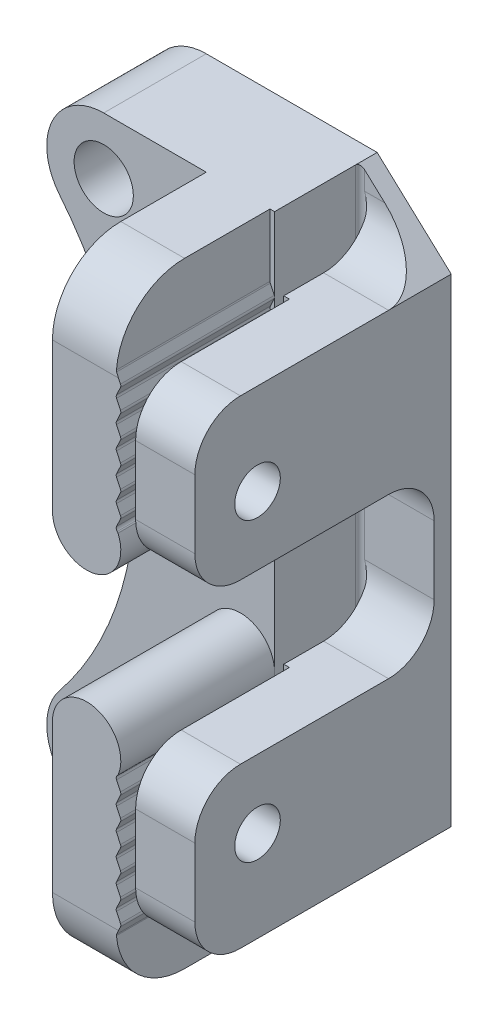
SolidWorks part; units mm, degrees
ref_plane "Front Plane" through (0, 0, 0) normal (0, 0, 1) x (1, 0, 0)
ref_plane "Top Plane" through (0, 0, 0) normal (0, 1, 0) x (1, 0, 0)
ref_plane "Right Plane" through (0, 0, 0) normal (1, 0, 0) x (0, 0, -1)
sketch "Sketch1" plane through (0, 0, 0) normal (0, 0, 1) x (1, 0, 0)
  line L1 (-10, 27) -> (5, 27)
  line L3 (-10, -27) -> (5, -27)
  line L4 (5, 27) -> (5, -27)
  circle A0 centre (0, 0) radius 2.6
  circle A1 centre (-10, 22) radius 2.6
  circle A2 centre (-10, -22) radius 2.6
  arc A3 (-13.8888, -18.8571) -> (-10, -27) centre (-10, -22) ccw
  arc A4 (-10, 27) -> (-13.8888, 18.8571) centre (-10, 22) ccw
  arc A5 (-13.8888, 18.8571) -> (-13.8888, -18.8571) centre (-37.2213, 0) cw
  dimension "D6" = 5.2
  dimension "D9" = 5
  dimension "D5" = 30
  dimension "D1" = 5
  dimension "D2" = 27
  dimension "D3" = 27
  dimension "D4" = 10
extrude "Boss-Extrude1" add sketch "Sketch1" along normal blind 9
sketch "Sketch2" plane through (0, 0, 9) normal (0, 0, 1) x (1, 0, 0)
  line L0 (5, -27) -> (5, 27) construction
  line L1 (5, -27) -> (5, -8)
  line L2 (5, 27) -> (-10, 27) construction
  line L3 (-10, -27) -> (5, -27) construction
  line L4 (5, 27) -> (-1, 27)
  line L5 (-1, -27) -> (5, -27)
  line L6 (-1, 8) -> (-1, 27)
  line L7 (-1, -8) -> (-1, -27)
  line L8 (5, 8) -> (5, 27)
  arc A0 (-1, 8) -> (5, 8) centre (2, 8) ccw
  arc A1 (5, -8) -> (-1, -8) centre (2, -8) ccw
  dimension "D2" = 10
  dimension "D1" = 6
  dimension "D3" = 5
extrude "Boss-Extrude2" add sketch "Sketch2" along normal offset from surface (13.5 mm away) 22.5 up to face at (-7.4, 22, 0)
sketch "Sketch3" plane through (5, 0, 0) normal (1, 0, 0) x (0, 0, -1)
  line L1 (0, -27) -> (0, 27) construction
  circle A0 centre (-17, 13) radius 2.6
  circle A1 centre (-5, 13) radius 2.6 construction
  circle A2 centre (-17, -13) radius 2.6
  circle A3 centre (-5, -13) radius 2.6 construction
  dimension "D5" = 5.2
  dimension "D1" = 13
  dimension "D2" = 13
  dimension "D3" = 5
  dimension "D4" = 12
extrude "Cut-Extrude1" cut sketch "Sketch3" against normal blind 30
fillet "Fillet1" radius 6 2 edges at (2, -27, 22.5) (2, 27, 22.5)
chamfer "Chamfer1" distance 1 angle 45 3 edges at (-7.4, 22, 0) (2.6, 0, 0) (-7.4, -22, 0)
sketch "Sketch4" plane through (0, 0, 0) normal (0, 0, -1) x (-1, 0, 0)
  line L0 (-5, 27) -> (-11.5, 21)
  line L1 (-11.5, 21) -> (-11.5, -21)
  line L2 (-11.5, -21) -> (-5, -27)
  line L3 (-5, -27) -> (-5, 27) construction
  line L5 (-5, 27) -> (-5, -27)
  arc A0 (-5, 8) -> (1, 8) centre (-2, 8) ccw construction
  arc A1 (1, -8) -> (-5, -8) centre (-2, -8) ccw construction
  point P10 (-2, -5)
  dimension "D2" = 16
  dimension "D1" = 6.5
  dimension "D3" = 16
extrude "Boss-Extrude3" add sketch "Sketch4" against normal blind 1.5
sketch "Sketch5" plane through (0, 0, 1.5) normal (0, 0, 1) x (1, 0, 0)
  line L0 (11.5, 21) -> (11.5, -21) construction
  line L1 (11.5, 7) -> (6.3, 7)
  line L2 (11.5, 7) -> (11.5, 21)
  line L3 (11.5, 21) -> (6.3, 21)
  line L4 (6.3, 7) -> (6.3, 21)
  line L5 (5, -27) -> (5, 27) construction
  line L6 (11.5, -21) -> (6.3, -21)
  line L7 (11.5, -21) -> (11.5, -7)
  line L8 (11.5, -7) -> (6.3, -7)
  line L9 (6.3, -21) -> (6.3, -7)
  dimension "D1" = 14
  dimension "D2" = 1.3
extrude "Boss-Extrude4" add sketch "Sketch5" along normal up to surface (21 mm away) up to face at (2, 13.75, 22.5)
sketch "Sketch6" plane through (11.5, 0, 0) normal (1, 0, 0) x (0, 0, -1)
  circle A0 centre (-17, 13) radius 2
  circle A1 centre (-17, -13) radius 2
  dimension "D1" = 4
extrude "Cut-Extrude2" cut sketch "Sketch6" against normal blind 6
sketch "Sketch7" plane through (0, 0, 1.5) normal (0, 0, 1) x (1, 0, 0)
  line L1 (6.3, -7) -> (5.8, -7)
  line L2 (6.3, -7) -> (6.3, -21)
  line L3 (6.3, -21) -> (5.8, -21)
  line L4 (5.8, -7) -> (5.8, -21)
  line L5 (6.3, 7) -> (5.8, 7)
  line L6 (6.3, 7) -> (6.3, 21)
  line L7 (6.3, 21) -> (5.8, 21)
  line L8 (5.8, 7) -> (5.8, 21)
  dimension "D1" = 0.5
extrude "Boss-Extrude5" add sketch "Sketch7" along normal up to surface (7.5 mm away) up to face at (-7.4, -22, 9)
fillet "Fillet5" radius 0.4 3 edges at (5.8, 14, 1.5) (5.8, -14, 1.5) (5, 0, 1.5)
fillet "Fillet3" radius 4 4 edges at (8.45, -7, 1.5) (8.45, 7, 1.5) (8.45, 21, 1.5) (8.45, -21, 1.5)
fillet "Fillet4" radius 4 4 edges at (8.9, 21, 22.5) (8.9, 7, 22.5) (8.9, -7, 22.5) (8.9, -21, 22.5)
sketch "Sketch8" plane through (0, 0, 22.5) normal (0, 0, 1) x (1, 0, 0)
  line L0 (5, -21) -> (5, -8) construction
  line L5 (4.6231, -9.6271) -> (4.9718, -10.3729)
  line L6 (4.9718, -10.6271) -> (4.6231, -11.3729)
  line L7 (4.6231, -11.6271) -> (4.9718, -12.3729)
  line L8 (4.9718, -12.6271) -> (4.6231, -13.3729)
  line L9 (4.6231, -13.6271) -> (4.9718, -14.3729)
  line L10 (4.6231, -15.3729) -> (4.9718, -14.6271)
  line L11 (4.9718, -16.3729) -> (4.6231, -15.6271)
  line L12 (4.9718, -16.6271) -> (4.6231, -17.3729)
  line L13 (4.6231, -17.6271) -> (4.9718, -18.3729)
  line L14 (4.6231, -19.3729) -> (4.9718, -18.6271)
  line L15 (4.9718, -20.3729) -> (4.6231, -19.6271)
  line L16 (4.9718, -20.6271) -> (4.6231, -21.3729)
  line L17 (4.5948, -21.5) -> (4.5948, -27)
  line L18 (5, -27) -> (-1, -27) construction
  line L19 (4.5948, -27) -> (5.4059, -27)
  line L20 (5.4059, -27) -> (5.4, -8)
  line L21 (5.4, -21) -> (5.4, -7) construction
  line L22 (5.4, -8) -> (5, -8)
  line L23 (4.6, -9.4446) -> (4.6, -8.2111) construction
  arc A0 (5, -8) -> (-1, -8) centre (2, -8) ccw construction
  arc A1 (4.7564, -9.1842) -> (5, -8) centre (2, -8) ccw
  arc A2 (4.6878, -9.2829) -> (4.7564, -9.1842) centre (4.4807, -9.0658) ccw
  arc A3 (4.6878, -9.2829) -> (4.6231, -9.6271) centre (4.8948, -9.5) ccw
  arc A4 (4.9718, -10.6271) -> (4.9718, -10.3729) centre (4.7, -10.5) ccw
  arc A5 (4.9718, -12.6271) -> (4.9718, -12.3729) centre (4.7, -12.5) ccw
  arc A6 (4.6231, -11.3729) -> (4.6231, -11.6271) centre (4.8948, -11.5) ccw
  arc A7 (4.6231, -13.3729) -> (4.6231, -13.6271) centre (4.8948, -13.5) ccw
  arc A8 (4.9718, -14.6271) -> (4.9718, -14.3729) centre (4.7, -14.5) ccw
  arc A9 (4.6231, -15.3729) -> (4.6231, -15.6271) centre (4.8948, -15.5) ccw
  arc A10 (4.9718, -16.6271) -> (4.9718, -16.3729) centre (4.7, -16.5) ccw
  arc A11 (4.6231, -17.3729) -> (4.6231, -17.6271) centre (4.8948, -17.5) ccw
  arc A12 (4.9718, -18.6271) -> (4.9718, -18.3729) centre (4.7, -18.5) ccw
  arc A13 (4.6231, -19.3729) -> (4.6231, -19.6271) centre (4.8948, -19.5) ccw
  arc A14 (4.9718, -20.6271) -> (4.9718, -20.3729) centre (4.7, -20.5) ccw
  arc A15 (4.6231, -21.3729) -> (4.5948, -21.5) centre (4.8948, -21.5) ccw
  dimension "D1" = 0.6
  dimension "D3" = 1.5
  dimension "D2" = 0.4
  dimension "D4" = 2
  dimension "D5" = 1
  dimension "D6" = 1
  dimension "D7" = 1
  dimension "D8" = 1
  dimension "D9" = 1
  dimension "D10" = 1
  dimension "D11" = 2
  dimension "D12" = 1
  dimension "D13" = 1
  dimension "D14" = 1
  dimension "D15" = 1
extrude "Cut-Extrude3" cut sketch "Sketch8" against normal up to surface (13.5 mm away) up to face at (6.05, -14, 9)
mirror "Mirror1" about plane through (0, 0, 0) normal (0, 1, 0) of "Cut-Extrude3"
